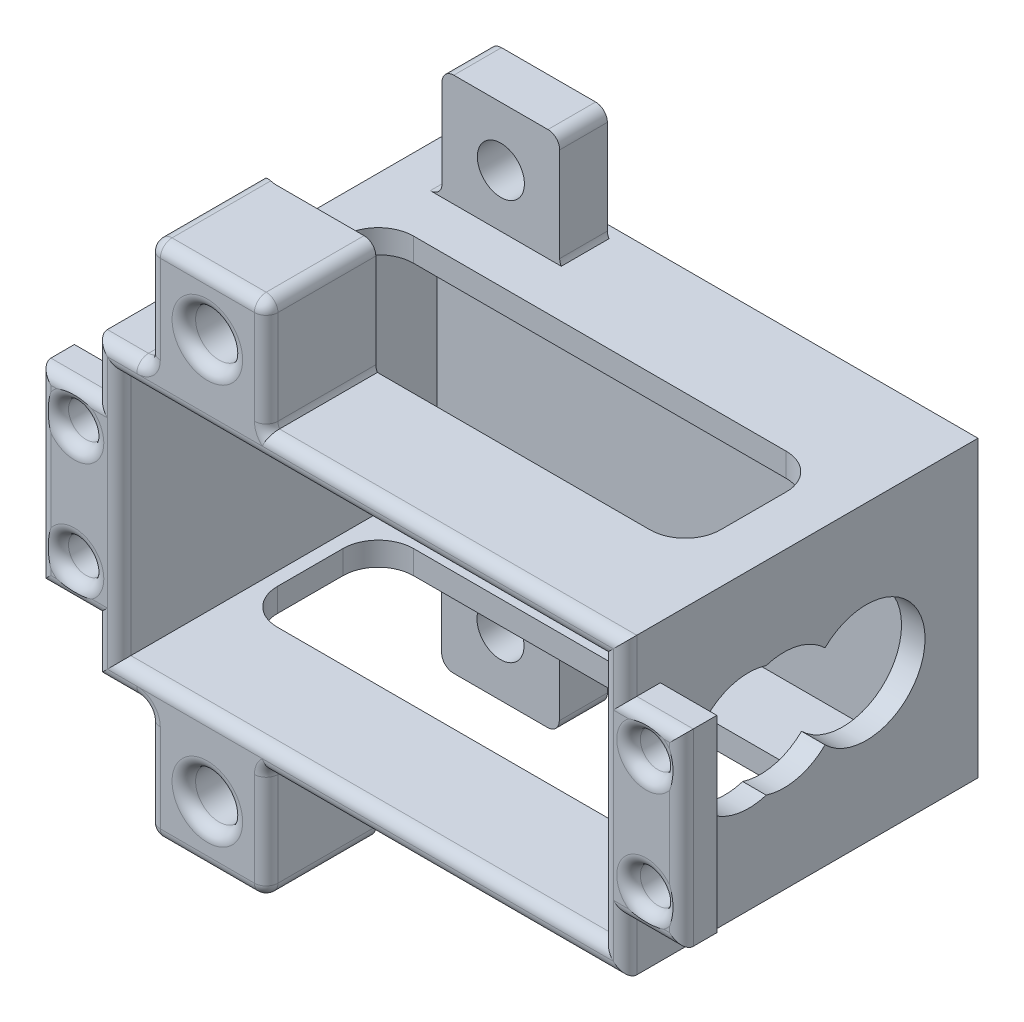
SolidWorks part; units mm, degrees
material "Custom Plastic"
ref_plane "Front Plane" through (0, 0, 0) normal (0, 0, 1) x (1, 0, 0)
ref_plane "Top Plane" through (0, 0, 0) normal (0, 1, 0) x (1, 0, 0)
ref_plane "Right Plane" through (0, 0, 0) normal (1, 0, 0) x (0, 0, -1)
sketch "Sketch1" plane through (0, 0, 0) normal (0, 0, 1) x (1, 0, 0)
  line L1 (-22.5, 12.5) -> (22.5, 12.5)
  line L2 (-22.5, 12.5) -> (-22.5, -12.5)
  line L3 (-22.5, -12.5) -> (22.5, -12.5)
  line L4 (22.5, 12.5) -> (22.5, -12.5)
  line L5 (-22.5, 12.5) -> (22.5, -12.5) construction
  line L6 (-22.5, -12.5) -> (22.5, 12.5) construction
  point P0 (0, 0)
  dimension "D1" = 45
  dimension "D2" = 25
extrude "Boss-Extrude2" add sketch "Sketch1" along normal blind 29
shell "Shell1" thickness 2 removed face at (0, 0, 29)
sketch "Sketch2" plane through (0, 0, 29) normal (0, 0, 1) x (1, 0, 0)
  line L0 (-27.3, 8) -> (-27.3, -8)
  line L1 (-20.5, 10.5) -> (20.5, 10.5)
  line L2 (-20.5, 10.5) -> (-20.5, -10.5)
  line L3 (-20.5, -10.5) -> (20.5, -10.5)
  line L4 (20.5, 10.5) -> (20.5, -10.5)
  line L5 (-24.3, 5) -> (24.3, 5) construction
  line L6 (-24.3, 5) -> (-24.3, -5) construction
  line L7 (-24.3, -5) -> (24.3, -5) construction
  line L8 (24.3, 5) -> (24.3, -5) construction
  line L9 (-24.3, 5) -> (24.3, -5) construction
  line L10 (-24.3, -5) -> (24.3, 5) construction
  line L11 (-27.3, -8) -> (27.3, -8)
  line L12 (27.3, 8) -> (27.3, -8)
  line L13 (-27.3, 8) -> (27.3, 8)
  line L14 (0, 0) -> (20.5, 0) construction
  line L15 (20.5, 10.5) -> (14.5, 10.5)
  line L16 (20.5, 13.5) -> (20.5, 16)
  line L17 (20.5, 16) -> (14.5, 16)
  line L18 (14.5, 13.5) -> (14.5, 16)
  line L19 (14.5, 10.5) -> (20.5, 16) construction
  line L20 (20.5, 10.5) -> (14.5, 16) construction
  line L21 (22.5, 12.5) -> (21.5, 12.5)
  line L22 (-22.5, 12.5) -> (13.5, 12.5)
  line L23 (-22.5, 12.5) -> (-22.5, -12.5)
  line L24 (-22.5, -12.5) -> (22.5, -12.5)
  line L25 (22.5, 12.5) -> (22.5, -12.5)
  line L27 (14.5, 13.5) -> (14.5, 10.5) construction
  line L28 (20.5, 13.5) -> (20.5, 10.5)
  line L29 (14.5, -13.5) -> (14.5, -16)
  line L30 (20.5, -13.5) -> (20.5, -16)
  line L31 (20.5, -16) -> (14.5, -16)
  line L32 (22.5, 12.5) -> (13.5, 12.5)
  line L33 (22.5, -12.5) -> (13.5, -12.5)
  line L34 (21.5, 12.5) -> (13.5, 12.5)
  line L35 (13.5, 12.5) -> (21.5, 12.5)
  line L37 (22.5, 12.5) -> (-22.5, 12.5)
  line L38 (22.5, 12.5) -> (22.5, -12.5)
  line L39 (22.5, -12.5) -> (-22.5, -12.5)
  line L40 (-22.5, 12.5) -> (-22.5, -12.5)
  arc A0 (14.5, 13.5) -> (13.5, 12.5) centre (13.5, 13.5) cw
  arc A1 (21.5, 12.5) -> (20.5, 13.5) centre (21.5, 13.5) cw
  arc A2 (21.5, -12.5) -> (20.5, -13.5) centre (21.5, -13.5) ccw
  arc A3 (14.5, -13.5) -> (13.5, -12.5) centre (13.5, -13.5) ccw
  point P6 (0, 0)
  line M13 (22.5, -12.5) -> (22.5, 12.5)
  line M15 (-22.5, 12.5) -> (-22.5, -12.5)
  dimension "D6" = 1
  dimension "D4" = 1
  dimension "D1" = 48.6
  dimension "D2" = 10
  dimension "D5" = 6
  dimension "D3" = 3
extrude "Boss-Extrude3" add sketch "Sketch2" against normal blind 3 contours L13 L0 L11 M15 | L13 L11 L12 M13 region at (-24.9, 0, 29) region at (24.9, 0, 29)
sketch "Sketch3" plane through (0, 0, 0) normal (0, 0, 1) x (1, 0, 0)
  line L0 (-27.3, 8) -> (-27.3, -8)
  line L1 (-20, 10) -> (20, 10)
  line L2 (-20, 10) -> (-20, -10)
  line L3 (-20, -10) -> (20, -10)
  line L4 (20, 10) -> (20, -10)
  line L5 (-24.3, 5) -> (24.3, 5) construction
  line L6 (-24.3, 5) -> (-24.3, -5) construction
  line L7 (-24.3, -5) -> (24.3, -5) construction
  line L8 (24.3, 5) -> (24.3, -5) construction
  line L9 (-24.3, 5) -> (24.3, -5) construction
  line L10 (-24.3, -5) -> (24.3, 5) construction
  line L11 (-27.3, -8) -> (27.3, -8)
  line L12 (27.3, 8) -> (27.3, -8)
  line L13 (-27.3, 8) -> (27.3, 8)
  line L14 (0, 5) -> (0, -5) construction
  line L15 (-20, 0) -> (20, 0) construction
  circle A0 centre (-24.3, 5) radius 1.5
  circle A1 centre (24.3, 5) radius 1.5
  circle A2 centre (-24.3, -5) radius 1.5
  circle A3 centre (24.3, -5) radius 1.5
  point P6 (0, 0)
  dimension "D4" = 3
  dimension "D1" = 48.6
  dimension "D2" = 10
  dimension "D3" = 3
extrude "Cut-Extrude1" cut sketch "Sketch3" along normal through all contours A1 | A3 | A0 | A2 region at (-24.3, 5, 0) region at (24.3, 5, 0) region at (-24.3, -5, 0) region at (24.3, -5, 0)
sketch "Sketch6" plane through (0, 0, 29) normal (0, 0, 1) x (1, 0, 0)
  line L0 (-18, 13.5) -> (-18, 21)
  line L1 (-7, 12) -> (22.5, 12)
  line L2 (-22, 12.5) -> (-22, -12.5)
  line L3 (-22, -12.5) -> (22.5, -12.5)
  line L4 (22.5, 12) -> (22.5, -12.5)
  line L5 (-22, 12.5) -> (-19, 12.5)
  line L6 (-22, 12.5) -> (-22, 22)
  line L7 (-17, 22) -> (-9, 22)
  line L8 (-8, 13) -> (-8, 21)
  line L9 (-8, 12) -> (-18, 22)
  line L10 (-22, 0) -> (0, 0) construction
  line L11 (-18, -13.5) -> (-18, -21)
  line L12 (-17, -22) -> (-9, -22)
  line L13 (-8, -13) -> (-8, -21)
  circle A0 centre (-13, 17) radius 2
  arc A1 (-7, 12) -> (-8, 13) centre (-7, 13) cw
  arc A2 (-8, 21) -> (-9, 22) centre (-9, 21) ccw
  arc A3 (-17, 22) -> (-18, 21) centre (-17, 21) ccw
  arc A4 (-18, 13.5) -> (-19, 12.5) centre (-19, 13.5) cw
  circle A5 centre (-13, -17) radius 2
  arc A6 (-18, -13.5) -> (-19, -12.5) centre (-19, -13.5) ccw
  arc A7 (-17, -22) -> (-18, -21) centre (-17, -21) cw
  arc A8 (-8, -21) -> (-9, -22) centre (-9, -21) cw
  arc A9 (-7, -12) -> (-8, -13) centre (-7, -13) ccw
  point P18 (-8, 22)
  line M28 (22.5, 12.5) -> (-22.5, 12.5)
  dimension "D4" = 34
  dimension "3.5" = 4
  dimension "D1" = 1
  dimension "D2" = 1
  dimension "D3" = 4
extrude "Boss-Extrude6" add sketch "Sketch6" against normal through all contours L7 A3 L9 A0 A1 L8 A2 M28 | L0 A4 L9 A0 A3 M28 | A9 L3 A6 L11 A7 L12 A8 L13 A5 region at (-15.0425, 15.5157, 29) region at (-11.1858, 18.8133, 29) region at (-13.433, -12.6464, 29)
sketch "Sketch7" plane through (20.5, 0, 0) normal (-1, 0, 0) x (0, 0, 1)
  line L0 (2, -10.5) -> (29, 10.5) construction
  line L1 (2, -10.5) -> (29, -10.5)
  line L2 (2, -10.5) -> (2, 10.5)
  line L3 (2, 10.5) -> (29, 10.5)
  line L4 (29, -10.5) -> (29, 10.5)
  circle A0 centre (15.5, 0) radius 5
  circle A1 centre (18.5, 0) radius 5
  circle A2 centre (8.5, 0) radius 5
  circle A3 centre (5.5, 0) radius 5
  dimension "D1" = 10
  dimension "D2" = 2
  dimension "D3" = 2
extrude "Cut-Extrude3" cut sketch "Sketch7" against normal blind 10 contours A3 A2 | A2 L0 A0 A3 | L0 A2 A0 | L0 A0 A2 | A3 A0 A2 | A0 L0 A2 | A2 A1 A0 | L0 A2 A0 A1 | L0 A1 A0 | A1 L0 A0 | L0 A0 A1 | A0 L0 A1 | A2 L0 A1 region at (20.5, -3.4208, 9.752) region at (20.5, -4.0436, 10.7878) region at (20.5, 0.1692, 11.9817) region at (20.5, -2.8058, 12.3035) region at (20.5, 0, 7) region at (20.5, -3.6435, 14.0463) region at (20.5, -1.2028, 13.4653) region at (20.5, 3.5548, 9.9749) region at (20.5, -1.1974, 17.55) region at (20.5, -0.592, 21.2307) region at (20.5, 4.2732, 19.2331) region at (20.5, 2.1204, 16.026) region at (20.5, 3.5548, 14.0251)
sketch "Sketch8" plane through (0, -10.5, 0) normal (0, 1, 0) x (1, 0, 0)
  line L1 (20.5, -2) -> (-20.5, -2)
  line L2 (20.5, -2) -> (20.5, -29)
  line L3 (20.5, -29) -> (-20.5, -29)
  line L4 (-20.5, -2) -> (-20.5, -29)
  line L5 (15.3014, -19.6826) -> (-16.3675, -19.6826)
  line L6 (18.3014, -16.6826) -> (18.3014, -11.1061)
  line L7 (15.3014, -8.1061) -> (-16.3675, -8.1061)
  line L8 (-19.3675, -16.6826) -> (-19.3675, -11.1061)
  arc A0 (18.3014, -16.6826) -> (15.3014, -19.6826) centre (15.3014, -16.6826) cw
  arc A1 (18.3014, -11.1061) -> (15.3014, -8.1061) centre (15.3014, -11.1061) ccw
  arc A2 (-16.3675, -8.1061) -> (-19.3675, -11.1061) centre (-16.3675, -11.1061) ccw
  arc A3 (-16.3675, -19.6826) -> (-19.3675, -16.6826) centre (-16.3675, -16.6826) cw
  dimension "D1" = 3
extrude "Cut-Extrude4" cut sketch "Sketch8" against normal through all both and the other way through all contours A3 L8 A2 L7 A1 L6 A0 L5
sketch "Sketch10" plane through (0, 0, 0) normal (0, 0, -1) x (-1, 0, 0)
  line L1 (-22.5, 12.5) -> (22.5, 12.5)
  line L2 (-22.5, 12.5) -> (-22.5, -12.5)
  line L3 (-22.5, -12.5) -> (22.5, -12.5)
  line L4 (22.5, 12.5) -> (22.5, -12.5)
  circle A0 centre (0, 0) radius 4.5
  circle A1 centre (-10, 0) radius 4.5
  dimension "D1" = 9
  dimension "D2" = 2
extrude "Boss-Extrude7" add sketch "Sketch10" along normal blind 1 contours L2 L1 L4 L3 | A1
sketch "Sketch11" plane through (0, 0, 0) normal (0, 0, -1) x (-1, 0, 0)
  circle A0 centre (0, 0) radius 17.3506
  circle A1 centre (-10, 0) radius 4.5
extrude "Boss-Extrude8" add sketch "Sketch11" along normal blind 9 and the other way blind 1 contours A1
sketch "Sketch15" plane through (0, -22, 0) normal (0, -1, 0) x (1, 0, 0)
  line L1 (-17, 8.1735) -> (-9, 8.1735)
  line L2 (-17, 8.1735) -> (-17, 0)
  line L3 (-17, 0) -> (-9, 0)
  line L4 (-9, 8.1735) -> (-9, 0)
  line L5 (-17, 4.0868) -> (-1.0481, 4.0868)
  line L6 (-17, 4.0868) -> (-17, 10.2697) construction
  line L7 (-17, 10.2697) -> (-1.0481, 10.2697)
  line L8 (-1.0481, 4.0868) -> (-1.0481, 10.2697)
  line L9 (-17, 4.0868) -> (-23.1686, 4.0868)
  line L10 (-17, 4.0868) -> (-17, 10.2697) construction
  line L11 (-17, 10.2697) -> (-23.1686, 10.2697)
  line L12 (-23.1686, 4.0868) -> (-23.1686, 10.2697)
  arc M13 (-16.3675, 8.1061) -> (-17, 8.1735) centre (-16.3675, 11.1061) cw
  line M14 (-17, 8.1735) -> (-17, 0)
  line M17 (-9, 8.1061) -> (-16.3675, 8.1061)
extrude "Cut-Extrude6" cut sketch "Sketch15" against normal up to surface (9.5 mm away) contours L12 L9 L1 L4 L5 L8 L7 L11 M14 | L5 L4 M14 M17 M13 region at (-17.2297, -22, 6.1301) region at (-13.0017, -22, 6.0973) up to face at (-4.3295, -12.5, 14.0524)
ref_plane "Plane1" through (0, 0, 0) normal (0, -1, 0) x (-1, 0, 0)
sketch "Sketch16" plane through (0, 22, 0) normal (0, 1, 0) x (1, 0, 0)
  line L1 (-9, -8.1061) -> (-17, -8.1061) construction
  line L2 (-9, -8.1061) -> (-9, 0) construction
  line L3 (-9, 0) -> (-17, 0)
  line L4 (-17, -8.1061) -> (-17, 0) construction
  line L5 (-9, -4.053) -> (-24.7668, -4.053)
  line L6 (-9, -4.053) -> (-9, -11.4021) construction
  line L7 (-9, -11.4021) -> (-24.7668, -11.4021)
  line L8 (-24.7668, -4.053) -> (-24.7668, -11.4021)
  line L9 (-9, -4.053) -> (0.201, -4.053)
  line L10 (-9, -4.053) -> (-9, -11.8862)
  line L11 (-9, -11.8862) -> (0.201, -11.8862)
  line L12 (0.201, -4.053) -> (0.201, -11.8862)
  line M1 (-17, 0) -> (-17, -8.1735)
  arc M2 (-17, -8.1735) -> (-16.3675, -8.1061) centre (-16.3675, -11.1061) cw
  line M3 (-16.3675, -8.1061) -> (-9, -8.1061)
  line M4 (-9, -8.1061) -> (-9, 0)
extrude "Cut-Extrude8" cut sketch "Sketch16" against normal up to surface (9.5 mm away) contours L12 L9 L10 L11 M4 | L10 L5 L8 L7 M3 M2 M1 | L5 M4 M1 M2 M3 region at (-13.0017, 22, 6.0805) region at (-4.3995, 22, 7.9696) region at (-18.3926, 22, 8.368) up to face at (-4.3295, 12.5, 14.0524)
fillet "Fillet1" radius 1 38 edges at (-11, -17, 29) (-11, 17, 29) (25.8, -5, 29) (7.317, -12.5, 29) (-7.9659, -12.7412, 29) (-8, -17, 29) (-8.2929, -21.7071, 29) (-13, -22, 29) (-17.7071, -21.7071, 29) (-18, -17.25, 29) (-18.2929, -12.7929, 29) (-20.75, -12.5, 29) (-22.5, -10.25, 29) (-24.9, -8, 29) (-27.3, 0, 29) (-24.9, 8, 29) (-22.5, 10.25, 29) (-20.75, 12.5, 29) (-18.2929, 12.7929, 29) (-18, 17.25, 29) (-17.7071, 21.7071, 29) (-13, 22, 29) (-8.2929, 21.7071, 29) (-8, 17, 29) (-7.9659, 12.7412, 29) (7.317, 12.5, 29) (22.5, 10.25, 29) (24.9, 8, 29) (27.3, 0, 29) (24.9, -8, 29) (22.5, -10.25, 29) (0, 10.5, 29) (-20.5, 0, 29) (0, -10.5, 29) (20.5, 0, 29) (25.8, 5, 29) (-22.8, -5, 29) (-22.8, 5, 29)
